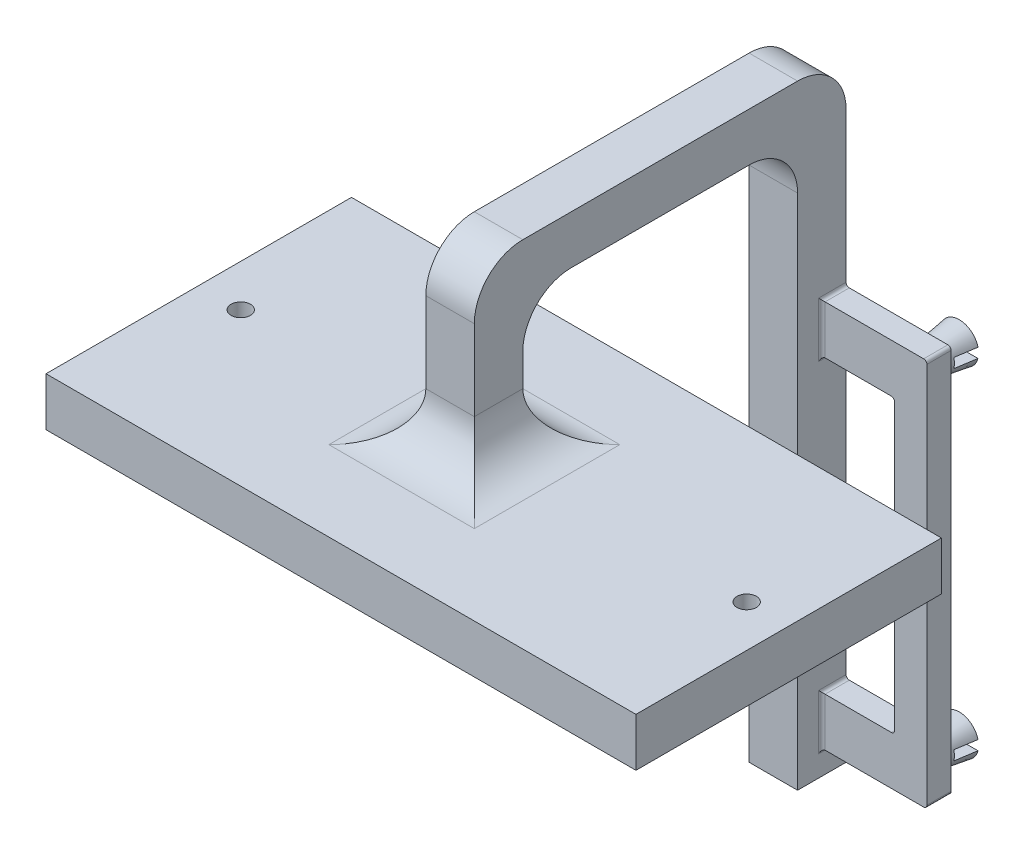
SolidWorks part; units mm, degrees
ref_plane "Ön Düzlem" through (0, 0, 0) normal (0, 0, 1) x (1, 0, 0)
ref_plane "Üst Düzlem" through (0, 0, 0) normal (0, 1, 0) x (1, 0, 0)
ref_plane "Sağ Düzlem" through (0, 0, 0) normal (1, 0, 0) x (0, 0, -1)
sketch "Çizim1" plane through (0, 0, 0) normal (0, 1, 0) x (1, 0, 0)
  line L13 (-14.05, 0) -> (-19.1293, 0) construction
  line L14 (0, 6.45) -> (0, 11.0365) construction
  line L22 (21.5293, 0) -> (16.45, 0) construction
  line L23 (0, -11.0365) -> (0, -6.45) construction
  line L24 (-19.1293, 11.0365) -> (21.5293, 11.0365)
  line L25 (-19.1293, 11.0365) -> (-19.1293, -11.0365)
  line L26 (-19.1293, -11.0365) -> (21.5293, -11.0365)
  line L27 (1.9, -6.45) -> (1.9, -3.2953)
  line L28 (1.9, -3.2953) -> (16.6263, -1.9922)
  line L29 (16.6263, 1.9922) -> (1.9, 3.2953)
  line L30 (1.9, 3.2953) -> (1.9, 6.45)
  line L31 (-1.9, 6.45) -> (-1.9, 2.8797)
  line L32 (-2.2091, 2.65) -> (-14.1591, 1.997)
  line L33 (-14.1591, -1.997) -> (-2.2091, -2.65)
  line L34 (-1.9, -2.8797) -> (-1.9, -6.45)
  line L35 (21.5293, 11.0365) -> (21.5293, -11.0365)
  arc A19 (-1.9, -6.45) -> (1.9, -6.45) centre (0, -6.45) ccw
  arc A20 (16.6263, -1.9922) -> (16.6263, 1.9922) centre (16.45, 0) ccw
  arc A21 (1.9, 6.45) -> (-1.9, 6.45) centre (0, 6.45) ccw
  arc A22 (-1.9, 2.8797) -> (-2.2091, 2.65) centre (0, 0) ccw
  arc A23 (-14.1591, 1.997) -> (-14.1591, -1.997) centre (-14.05, 0) ccw
  arc A24 (-2.2091, -2.65) -> (-1.9, -2.8797) centre (0, 0) ccw
extrude "Yükseklik-Ekstrüzyon3" add sketch "Çizim1" along normal blind 1.5 contours L25 L30 L29 region at (1.2, 0, -10.5738)
sketch "Çizim10" plane through (0, 1.5, 0) normal (0, 1, 0) x (1, 0, 0)
  line L4 (21.5293, -11.0365) -> (21.5293, 11.0365)
  line L5 (21.5293, 11.0365) -> (-19.1293, 11.0365)
  line L6 (-19.1293, 11.0365) -> (-19.1293, -11.0365)
  line L7 (-19.1293, -11.0365) -> (21.5293, -11.0365)
  line L8 (21.5293, -11.0365) -> (21.5293, 11.0365)
  line L9 (21.5293, 11.0365) -> (-19.1293, 11.0365)
  line L10 (-19.1293, 11.0365) -> (-19.1293, -11.0365)
  line L11 (-19.1293, -11.0365) -> (21.5293, -11.0365)
  dimension "D1" = 0
extrude "Yükseklik-Ekstrüzyon5" add sketch "Çizim10" along normal blind 1.5
sketch "Çizim11" plane through (0, 0, 0) normal (1, 0, 0) x (0, 0, -1)
  line L2 (18.5, 10.9809) -> (1.5, 10.9809)
  line L3 (18.5, 10.9809) -> (18.5, -24.0191)
  line L4 (1.5, 1.7777) -> (1.5, 10.9809)
  line L5 (1.5, 13.9809) -> (21.5, 13.9809)
  line L6 (21.5, 13.9809) -> (21.5, -24.0191)
  line L7 (-1.5, 1.7777) -> (-1.5, 10.9809)
  line L8 (18.5, -24.0191) -> (21.5, -24.0191)
  line L9 (1.5, 1.7777) -> (-1.5, 1.7777)
  line L10 (0, 1.7777) -> (0, 10.9809) construction
  line L11 (18.5, 10.9809) -> (18.5, 13.9809) construction
  line L12 (18.5, 12.4809) -> (-13.0492, 12.4809) construction
  line L13 (18.5, 12.4809) -> (21.5, 12.4809) construction
  line L14 (20, 12.4809) -> (20, -24.0191) construction
  line L15 (1.5, 13.9809) -> (-1.5, 13.9809)
  line L16 (-1.5, 13.9809) -> (-1.5, 10.9809)
  line L18 (0, 12.4809) -> (0, 15.9654) construction
  dimension "D1" = 20
  dimension "D2" = 3
  dimension "D3" = 3
  dimension "D4" = 3
  dimension "D5" = 36.5
extrude "Yükseklik-Ekstrüzyon6" add sketch "Çizim11" along normal mid plane 3
sketch "Çizim12" plane through (0, 0, 0) normal (0, 1, 0) x (1, 0, 0)
  line L0 (-14.05, 0) -> (-17.05, 0) construction
  line L1 (19.45, 0) -> (16.45, 0) construction
  line L2 (0, -6.45) -> (0, -9.45) construction
  line L3 (0, 9.45) -> (0, 6.45) construction
  line L4 (0, -9.45) -> (-17.05, -9.45)
  line L5 (-17.05, -9.45) -> (-17.05, 9.45)
  line L6 (-17.05, 9.45) -> (19.45, 9.45)
  line L7 (19.45, 9.45) -> (19.45, -9.45)
  line L8 (19.45, -9.45) -> (0, -9.45)
  line L10 (-19.1293, -11.0365) -> (21.5293, -11.0365)
  line L11 (-19.1293, -11.0365) -> (-19.1293, 11.0365)
  line L12 (-19.1293, 11.0365) -> (21.5293, 11.0365)
  line L13 (21.5293, -11.0365) -> (21.5293, 11.0365)
  dimension "D1" = 3
  dimension "D2" = 3
extrude "Kes-Ekstrüzyon1" cut sketch "Çizim12" along normal blind 5 and the other way blind 3
fillet "Radyus1" radius 3 8 edges at (0, 3, -1.5) (-1.5, 3, 0) (1.5, 3, 0) (0, 3, 1.5) (0, 13.9809, 1.5) (0, 10.9809, -1.5) (0, 13.9809, -21.5) (0, 10.9809, -18.5)
ref_plane "Düzlem1" through (0, 0, -20) normal (0, 0, -1) x (-1, 0, 0)
sketch "Çizim13" plane through (0, 0, -20) normal (0, 0, -1) x (-1, 0, 0)
  line L1 (-6.5, -21.0191) -> (0, -21.0191) construction
  line L2 (-6.5, -0.0191) -> (-6.5, -21.0191) construction
  line L3 (0, 1.5) -> (0, -1.5)
  line L6 (0, -1.5) -> (-8, -1.5)
  line L8 (0, 1.5) -> (-8, 1.5)
  line L9 (-8, -1.5) -> (-8, 1.5)
  line L10 (0, -0.3462) -> (-8, 1.5) construction
  line L11 (0, 0.3462) -> (-8, -1.5) construction
  line L16 (0, -22.5191) -> (-8, -22.5191)
  line L18 (0, -19.5191) -> (-8, -19.5191)
  line L19 (-8, -22.5191) -> (-8, -19.5191)
  line L20 (0, -21.0191) -> (-8, -19.5191) construction
  line L21 (0, -21.0191) -> (-8, -22.5191) construction
  line L22 (0, -19.5191) -> (0, -22.5191)
extrude "Yükseklik-Ekstrüzyon7" add sketch "Çizim13" along normal up to surface (1.5 mm away) up to face at (0, -6.5191, -21.5)
fillet "Radyus2" radius 0.2 6 edges at (1.5, 1.5, -20.75) (1.5, 0, -20) (1.5, -1.5, -20.75) (1.5, -19.5191, -20.75) (1.5, -21.0191, -20) (1.5, -22.5191, -20.75)
sketch "Çizim14" plane through (0, 0, -21.5) normal (0, 0, -1) x (-1, 0, 0)
  line L1 (-8, 0) -> (-6.5, 0) construction
  line L2 (-8, -1.5) -> (-8, 1.5) construction
  line L3 (-19.45, 0) -> (17.05, 0) construction
  circle A0 centre (-6.5, 0) radius 1
ref_plane "Düzlem2" through (6.5, 0, 0) normal (1, 0, 0) x (0, 0, -1)
sketch "Çizim17" plane through (0, 0, -21.5) normal (0, 0, -1) x (-1, 0, 0)
  line L0 (-8, -19.5191) -> (-1.7, -19.5191) construction
  line L1 (-8, -1.5) -> (-6, -1.5)
  line L2 (-8, -1.5) -> (-8, -19.5191)
  line L3 (-8, -19.5191) -> (-6, -19.5191)
  line L4 (-6, -1.5) -> (-6, -19.5191)
extrude "Yükseklik-Ekstrüzyon8" add sketch "Çizim17" against normal up to surface (1.5 mm away) up to face at (4.85, 0, -20)
fillet "Radyus3" radius 0.2 4 edges at (8, 1.5, -20.75) (8, -22.5191, -20.75) (6, -19.5191, -20.75) (6, -1.5, -20.75)
sketch "Çizim15" plane through (6.5, 0, 0) normal (1, 0, 0) x (0, 0, -1)
  line L0 (21.5, 0) -> (23.5, 0) construction
  line L1 (21.5, -1) -> (21.5, 1) construction
  line L2 (23.5, 0) -> (23.5, 1.2)
  line L3 (23.5, 1.2) -> (21.5, 0.9)
  line L4 (21.5, 0) -> (23.5, 0)
  line L5 (21.5, 0.9) -> (21.5, 0)
  dimension "D1" = 0.9
  dimension "D2" = 1.2
revolve "Döndür1" add sketch "Çizim15" angle 360 about L0
sketch "Çizim16" plane through (6.5, 0, 0) normal (1, 0, 0) x (0, 0, -1)
  line L0 (23.5, 0) -> (22.2, 0) construction
  line L1 (23.5, -1.2) -> (23.5, 1.2) construction
  line L3 (23.5, 0.3) -> (22.2, 0.3)
  line L4 (23.5, -0.3) -> (22.2, -0.3)
  line L6 (23.5, 0.3) -> (23.5, -0.3)
  line L7 (22.2, 0.3) -> (22.2, -0.3)
  line L8 (23.5, -0.3) -> (21.5, -0.3) construction
  line L9 (23.5, 0) -> (21.5, 0) construction
  line L10 (23.5, 0.3) -> (21.5, 0.3) construction
  dimension "D1" = 0.3
  dimension "D3" = 1.3
  dimension "D2" = 0.3
extrude "Kes-Ekstrüzyon2" cut sketch "Çizim16" against normal blind 2 and the other way blind 3
ref_plane "Düzlem3" through (0, -10.5095, 0) normal (0, -1, 0) x (-1, 0, 0)
mirror "Aynalama1" about plane through (0, -10.5095, 0) normal (0, -1, 0) of "Döndür1", "Kes-Ekstrüzyon2"
sketch "Çizim18" plane through (0, 1.5, 0) normal (0, -1, 0) x (1, 0, 0)
  line L0 (-16.05, 0) -> (-14.45, 0) construction
  line L1 (18.45, 0) -> (16.85, 0) construction
  arc A0 (-14.1591, 1.997) -> (-14.1591, -1.997) centre (-14.05, 0) ccw construction
  circle A1 centre (-14.45, 0) radius 0.6
  arc A2 (16.6263, -1.9922) -> (16.6263, 1.9922) centre (16.45, 0) ccw construction
  circle A3 centre (16.85, 0) radius 0.6
extrude "Kes-Ekstrüzyon3" cut sketch "Çizim18" against normal blind 3 and the other way blind 7
